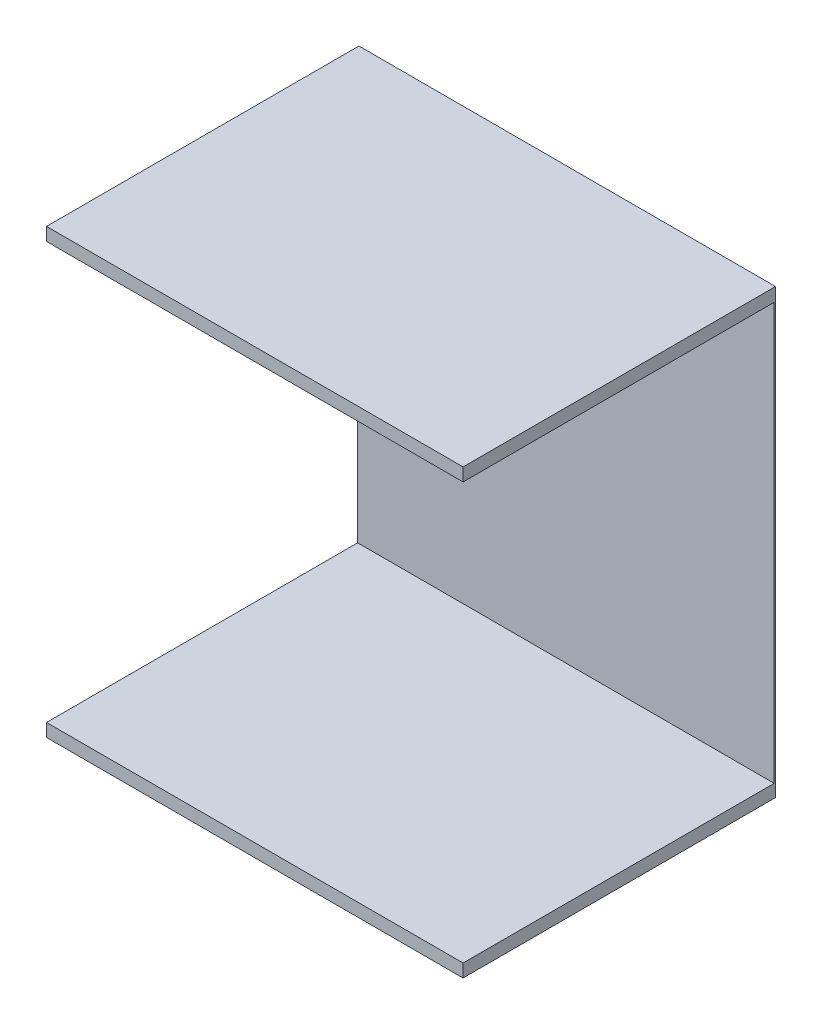
SolidWorks part; units mm, degrees
ref_plane "Front Plane" through (0, 0, 0) normal (0, 0, 1) x (1, 0, 0)
ref_plane "Top Plane" through (0, 0, 0) normal (0, 1, 0) x (1, 0, 0)
ref_plane "Right Plane" through (0, 0, 0) normal (1, 0, 0) x (0, 0, -1)
sketch "Sketch1" plane through (0, 0, 0) normal (0, 0, 1) x (1, 0, 0)
  line L2 (0, 0) -> (0, 6.35)
  line L3 (0, 6.35) -> (203.2, 6.35)
  line L5 (0, -209.55) -> (203.2, -209.55)
  line L6 (0, -209.55) -> (0, -203.2)
  line L7 (0, -203.2) -> (203.2, -203.2)
  line L8 (203.2, -209.55) -> (203.2, -203.2)
  line L10 (400.0965, -209.55) -> (406.4, -208.7829)
  line L12 (0, -203.2) -> (0, 0)
  line L13 (203.2, -209.55) -> (400.0965, -209.55)
  line L14 (0, 0) -> (203.2, 0)
  line L15 (203.2, 0) -> (203.2, 6.35)
  dimension "D1" = 203.2
  dimension "D2" = 6.35
  dimension "D3" = 6.35
  dimension "D4" = 203.2
  dimension "D5" = 0
  dimension "D6" = 6.35
  dimension "D7" = 6.35
extrude "Boss-Extrude1" add sketch "Sketch1" along normal blind 152.4 contours L10 L3 L2 | L5 L8 L7 L6 region at (101.6, -206.375, 0) region at (101.6, 3.175, 0)
sketch "Sketch3" plane through (0, 0, 0) normal (0, 0, -1) x (-1, 0, 0)
  line L4 (0, -206.375) -> (-203.2, -209.55)
  line L5 (0, -209.55) -> (0, -203.2) construction
  line L6 (-203.2, -209.55) -> (-203.2, 6.35)
  line L7 (-203.2, 6.35) -> (0, 6.35)
  line L8 (0, 6.35) -> (0, -206.375)
extrude "Boss-Extrude2" add sketch "Sketch3" against normal blind 0.635
